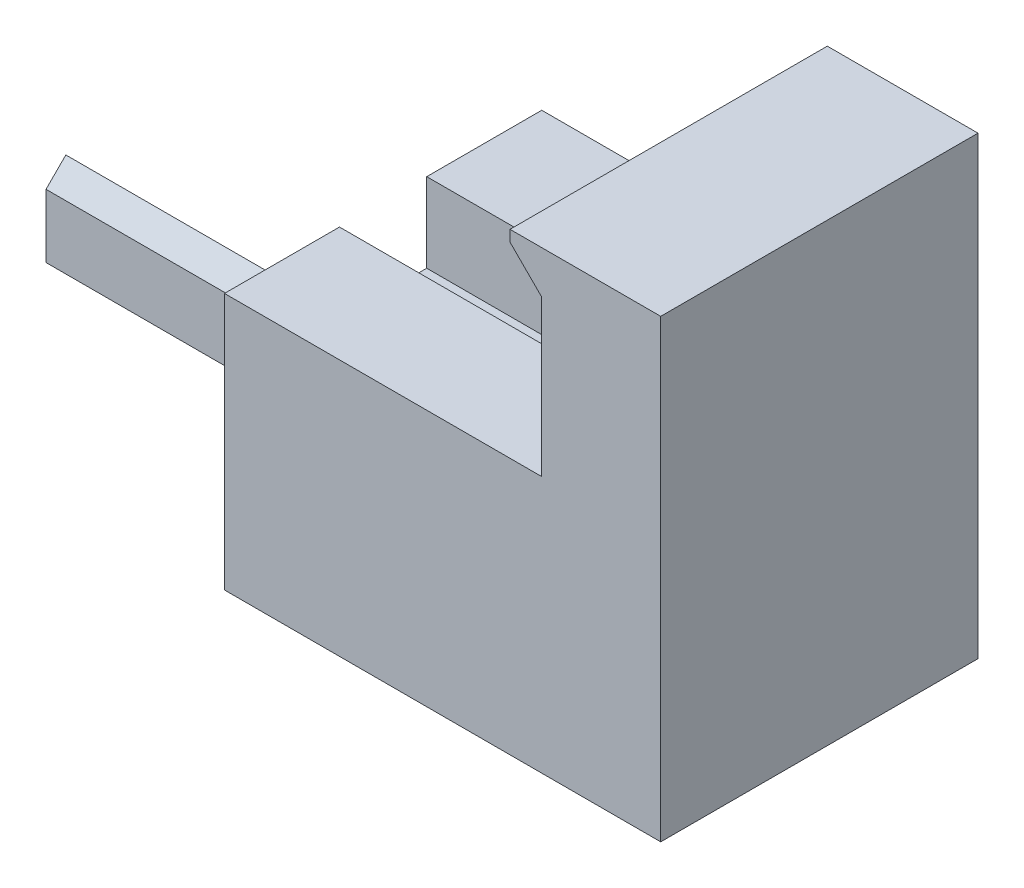
SolidWorks part; units mm, degrees
ref_plane "Plan de face" through (0, 0, 0) normal (0, 0, 1) x (1, 0, 0)
ref_plane "Plan de dessus" through (0, 0, 0) normal (0, 1, 0) x (1, 0, 0)
ref_plane "Plan de droite" through (0, 0, 0) normal (1, 0, 0) x (0, 0, -1)
sketch "Esquisse1" plane through (0, 0, 0) normal (0, 1, 0) x (1, 0, 0)
  line L1 (0, 0) -> (27.5, 0)
  line L2 (0, 0) -> (0, 20)
  line L3 (0, 20) -> (27.5, 20)
  line L4 (27.5, 0) -> (27.5, 20)
  dimension "D1" = 27.5
  dimension "D2" = 20
extrude "Boss.-Extru.1" add sketch "Esquisse1" along normal blind 16.19
sketch "Esquisse2" plane through (0, 16.19, 0) normal (0, 1, 0) x (1, 0, 0)
  line L0 (0, 0) -> (27.5, 0) construction
  line L1 (27.5, 20) -> (20, 20)
  line L2 (27.5, 20) -> (27.5, 0)
  line L3 (27.5, 0) -> (20, 0)
  line L4 (20, 20) -> (20, 0)
  dimension "D1" = 7.5
extrude "Boss.-Extru.2" add sketch "Esquisse2" along normal blind 12.5
sketch "Esquisse4" plane through (0, 0, 0) normal (-1, 0, 0) x (0, 0, 1)
  line L0 (-10, 16.19) -> (-10, 0) construction
  line L1 (-20, 16.19) -> (0, 16.19) construction
  line L2 (-20, 0) -> (0, 0) construction
  line L3 (-8.75, 7.5) -> (-8.75, 3.5)
  line L12 (-11.25, 7.5) -> (-11.25, 3.5)
  line L13 (-11.25, 7.5) -> (-10, 8.75)
  line L14 (-10, 8.75) -> (-8.75, 7.5)
  line L15 (-8.75, 3.5) -> (-10, 2.25)
  line L16 (-10, 2.25) -> (-11.25, 3.5)
  line L17 (-11.25, 5.5) -> (-8.75, 5.5) construction
  dimension "D1" = 2.5
  dimension "D2" = 4
  dimension "D3" = 5.5
extrude "Boss.-Extru.4" add sketch "Esquisse4" along normal blind 20
sketch "Esquisse5" plane through (0, 16.19, 0) normal (0, 1, 0) x (1, 0, 0)
  line L0 (0, 10) -> (20, 10) construction
  line L1 (0, 20) -> (0, 0) construction
  line L2 (20, 20) -> (20, 0) construction
  line L3 (15, 12.75) -> (0, 12.75)
  line L4 (15, 7.25) -> (0, 7.25)
  line L7 (0, 12.75) -> (0, 7.25)
  line L8 (15, 12.75) -> (15, 7.25)
  dimension "D1" = 5.5
  dimension "D2" = 2.75
  dimension "D3" = 15
extrude "Enlèv. mat.-Extru.1" cut sketch "Esquisse5" against normal blind 5
sketch "Esquisse11" plane through (0, 0, -12.75) normal (0, 0, 1) x (1, 0, 0)
  line L0 (15, 13.69) -> (0.1466, 13.69) construction
  line L1 (15, 11.19) -> (15, 16.19) construction
  circle A0 centre (11.7751, 13.69) radius 1
  dimension "D1" = 2
extrude "Boss.-Extru.5" add sketch "Esquisse11" along normal up to surface (5.5 mm away) up to face at (7.5, 13.69, -7.25)
sketch "Esquisse12" plane through (20, 0, 0) normal (-1, 0, 0) x (0, 0, 1)
  line L0 (0, 28.69) -> (0, 16.19) construction
  line L1 (-20, 28.69) -> (0, 28.69)
  line L2 (-20, 28.69) -> (-20, 25.99)
  line L3 (-20, 25.99) -> (0, 25.99)
  line L4 (0, 28.69) -> (0, 25.99)
  line L5 (-20, 16.19) -> (0, 16.19) construction
  dimension "D1" = 9.8
extrude "Boss.-Extru.6" add sketch "Esquisse12" along normal blind 2
chamfer "Chanfrein1" distance 2 angle 45 1 edges at (18, 25.99, -10)
